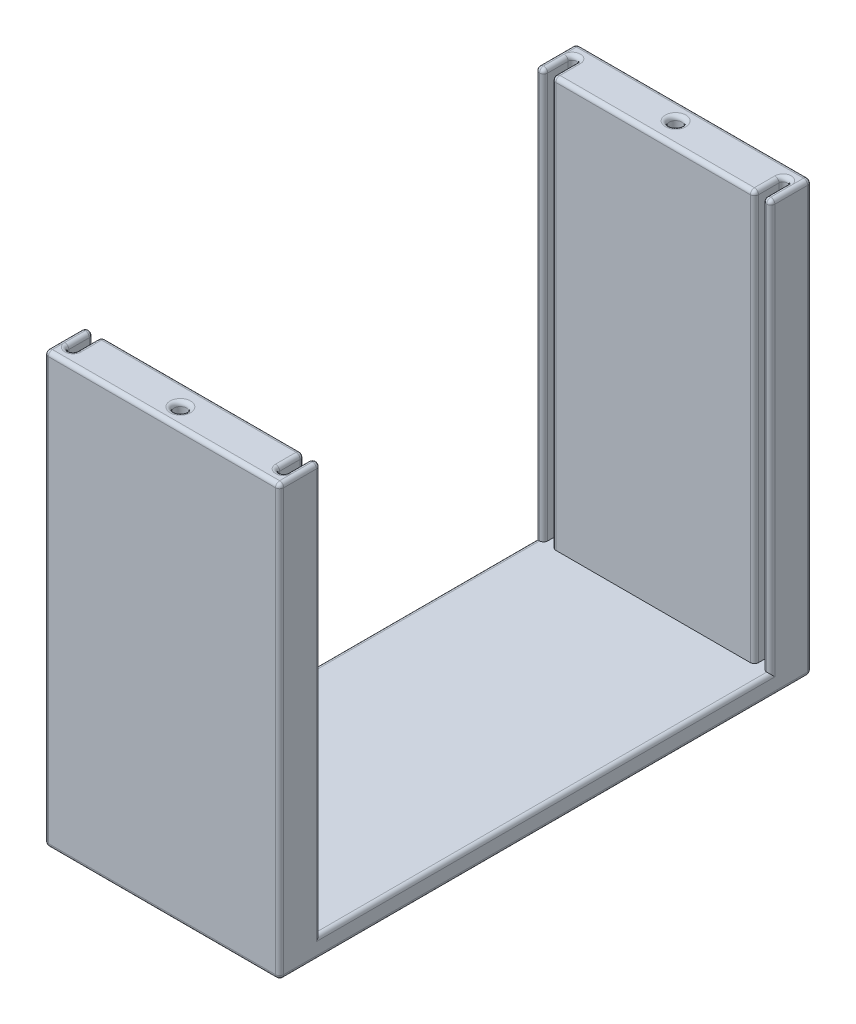
SolidWorks part; units mm, degrees
ref_plane "Front Plane" through (0, 0, 0) normal (0, 0, 1) x (1, 0, 0)
ref_plane "Top Plane" through (0, 0, 0) normal (0, 1, 0) x (1, 0, 0)
ref_plane "Right Plane" through (0, 0, 0) normal (1, 0, 0) x (0, 0, -1)
sketch "Sketch4" plane through (0, 0, 0) normal (0, 1, 0) x (1, 0, 0)
  line L0 (-28.75, 0) -> (28.75, 0) construction
  line L1 (-28.75, -65) -> (28.75, -65)
  line L2 (-28.75, -65) -> (-28.75, 65)
  line L3 (-28.75, 65) -> (28.75, 65)
  line L4 (28.75, -65) -> (28.75, 65)
  line L5 (-28.75, -65) -> (28.75, 65) construction
  line L6 (-28.75, 65) -> (28.75, -65) construction
  line L7 (0, -65) -> (0, 65) construction
  circle A0 centre (0, -60.5) radius 1.5
  circle A1 centre (0, 60.5) radius 1.5
  point P0 (0, 0)
  dimension "D3" = 3
  dimension "D4" = 3
  dimension "D5" = 0
  dimension "D1" = 130
  dimension "D2" = 57.5
extrude "Boss-Extrude3" add sketch "Sketch4" along normal blind 5
sketch "Sketch5" plane through (0, 5, 0) normal (0, 1, 0) x (1, 0, 0)
  line L0 (27.75, -55) -> (28.75, -55)
  line L5 (28.75, -65) -> (28.75, 65) construction
  line L10 (0, -65) -> (0, 65) construction
  line L11 (-28.75, -65) -> (28.75, -65)
  line L12 (28.75, 65) -> (-28.75, 65) construction
  line L30 (-28.75, -65) -> (-28.75, -55)
  line L31 (-28.75, -55) -> (-27.75, -55)
  line L32 (28.75, -65) -> (28.75, -55)
  line L33 (-28.75, 0) -> (28.75, 0) construction
  line L35 (26.75, -56) -> (26.75, -61)
  line L37 (24.75, -56) -> (24.75, -61)
  line L38 (-28.75, 65) -> (-28.75, -65) construction
  line L39 (-24.75, -56) -> (-24.75, -61)
  line L41 (-26.75, -56) -> (-26.75, -61)
  line L42 (-23.75, -55) -> (23.75, -55)
  line L43 (28.75, 65) -> (28.75, 55)
  line L44 (27.75, 55) -> (28.75, 55)
  line L45 (26.75, 56) -> (26.75, 61)
  line L47 (24.75, 56) -> (24.75, 61)
  line L48 (-23.75, 55) -> (23.75, 55)
  line L49 (-24.75, 56) -> (-24.75, 61)
  line L51 (-26.75, 56) -> (-26.75, 61)
  line L52 (-28.75, 55) -> (-27.75, 55)
  line L53 (-28.75, 65) -> (-28.75, 55)
  line L54 (-28.75, 65) -> (28.75, 65)
  arc A0 (27.75, -55) -> (26.75, -56) centre (27.75, -56) ccw
  arc A1 (23.75, -55) -> (24.75, -56) centre (23.75, -56) cw
  arc A4 (-23.75, -55) -> (-24.75, -56) centre (-23.75, -56) ccw
  arc A7 (-27.75, -55) -> (-26.75, -56) centre (-27.75, -56) cw
  arc A8 (27.75, 55) -> (26.75, 56) centre (27.75, 56) cw
  arc A11 (23.75, 55) -> (24.75, 56) centre (23.75, 56) ccw
  arc A12 (-23.75, 55) -> (-24.75, 56) centre (-23.75, 56) cw
  arc A15 (-27.75, 55) -> (-26.75, 56) centre (-27.75, 56) ccw
  circle A16 centre (0, -60.5) radius 1.5
  circle A17 centre (0, 60.5) radius 1.5
  arc A18 (24.75, -61) -> (26.75, -61) centre (25.75, -61) ccw
  arc A19 (-24.75, -61) -> (-26.75, -61) centre (-25.75, -61) cw
  arc A20 (-24.75, 61) -> (-26.75, 61) centre (-25.75, 61) ccw
  arc A21 (24.75, 61) -> (26.75, 61) centre (25.75, 61) cw
  point P12 (26.75, -55)
  dimension "D5" = 1
  dimension "D6" = 1
  dimension "D7" = 0
  dimension "D8" = 6
  dimension "D9" = 0
  dimension "D10" = 3
  dimension "D11" = 3
  dimension "D2" = 0
  dimension "D1" = 10
  dimension "D3" = 2
  dimension "D4" = 2
extrude "Boss-Extrude4" add sketch "Sketch5" along normal blind 100
fillet "Fillet2" radius 1 50 edges at (0, 0, -62) (0, 0, 62) (0, 105, 62) (-28.25, 105, 55) (-27.0429, 105, 55.2929) (-26.75, 105, 58.5) (-24.75, 105, 58.5) (-24.4571, 105, 55.2929) (0, 105, 55) (24.4571, 105, 55.2929) (24.75, 105, 58.5) (26.75, 105, 58.5) (27.0429, 105, 55.2929) (28.25, 105, 55) (0, 105, 65) (0, 0, 65) (-28.75, 55, -55) (-28.75, 5, 0) (-28.75, 55, 55) (-28.75, 105, 60) (-28.75, 52.5, 65) (-28.75, 0, 0) (0, 105, -62) (28.25, 105, -55) (27.0429, 105, -55.2929) (26.75, 105, -58.5) (24.75, 105, -58.5) (24.4571, 105, -55.2929) (0, 105, -55) (-24.4571, 105, -55.2929) (-24.75, 105, -58.5) (-26.75, 105, -58.5) (-27.0429, 105, -55.2929) (-28.25, 105, -55) (-28.75, 105, -60) (0, 105, -65) (-28.75, 52.5, -65) (0, 0, -65) (28.75, 52.5, 65) (28.75, 105, 60) (28.75, 55, 55) (28.75, 5, 0) (28.75, 55, -55) (28.75, 105, -60) (28.75, 52.5, -65) (28.75, 0, 0) (-25.75, 105, 62) (25.75, 105, 62) (25.75, 105, -62) (-25.75, 105, -62)
